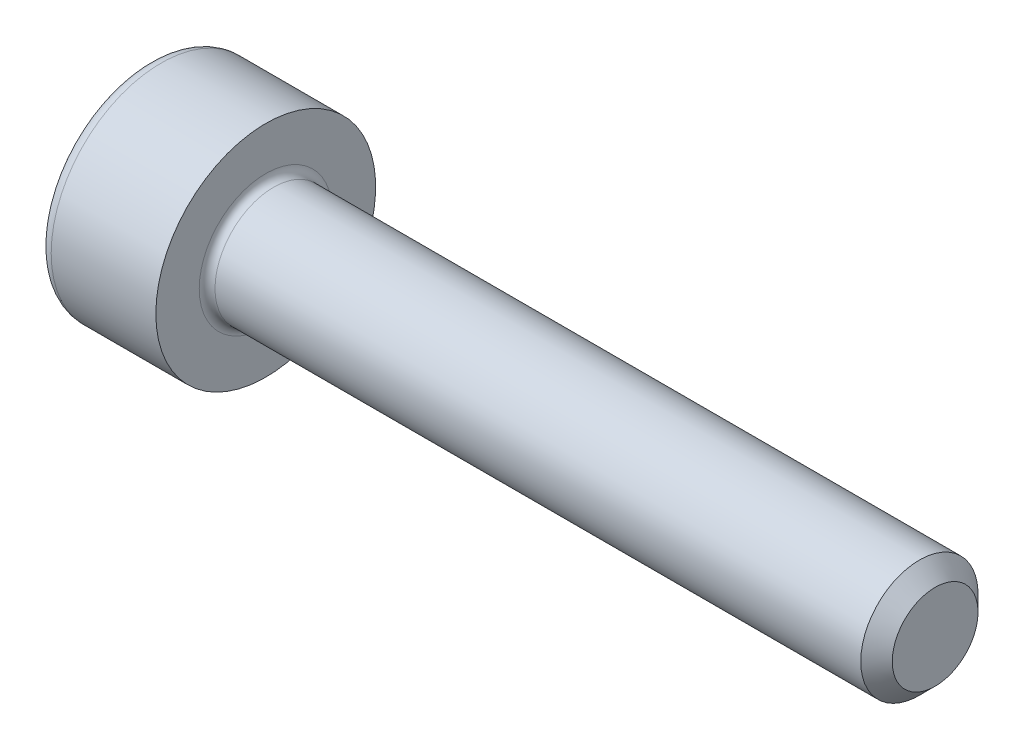
SolidWorks part; units mm, degrees
ref_plane "Спереди" through (0, 0, 0) normal (0, 0, 1) x (1, 0, 0)
ref_plane "Сверху" through (0, 0, 0) normal (0, 1, 0) x (1, 0, 0)
ref_plane "Справа" through (0, 0, 0) normal (1, 0, 0) x (0, 0, -1)
sketch "Sketch1" plane through (0, 0, 0) normal (0, 0, 1) x (1, 0, 0)
  line L0 (0, 0) -> (1.4887, 0)
  line L1 (1.4887, 0) -> (1.4887, 1.3957)
  line L2 (1.4887, 1.3957) -> (0, 1.3957)
  line L3 (0, 1.3957) -> (0, 0)
  line L4 (1.4887, 0) -> (9.9887, 0)
  line L5 (9.9887, 0) -> (9.9887, 0.7444)
  line L6 (9.9887, 0.7444) -> (1.4887, 0.7444)
  dimension "D1" = 8.5
revolve "Revolve1" add sketch "Sketch1" angle 360 about L0 region at (0.7444, 0.6978, 0) region at (5.7387, 0.3722, 0)
fillet "Fillet1" radius 0.1 1 edges at (1.4887, 0, 0.7444)
fillet "Fillet2" radius 0.16 1 edges at (0, 0, 1.3957)
chamfer "Chamfer1" distance 0.2 angle 45 1 edges at (9.9887, 0, 0.7444)
sketch "Sketch2" plane through (0, 0, 0) normal (-1, 0, 0) x (0, 0, 1)
  line L1 (0, 0.8776) -> (-0.76, 0.4388)
  line L2 (-0.76, 0.4388) -> (-0.76, -0.4388)
  line L3 (-0.76, -0.4388) -> (0, -0.8776)
  line L4 (0, -0.8776) -> (0.76, -0.4388)
  line L5 (0.76, -0.4388) -> (0.76, 0.4388)
  line L6 (0.76, 0.4388) -> (0, 0.8776)
  circle A0 centre (0, 0) radius 0.76 construction
extrude "Extrude1" cut sketch "Sketch2" against normal blind 0.7
